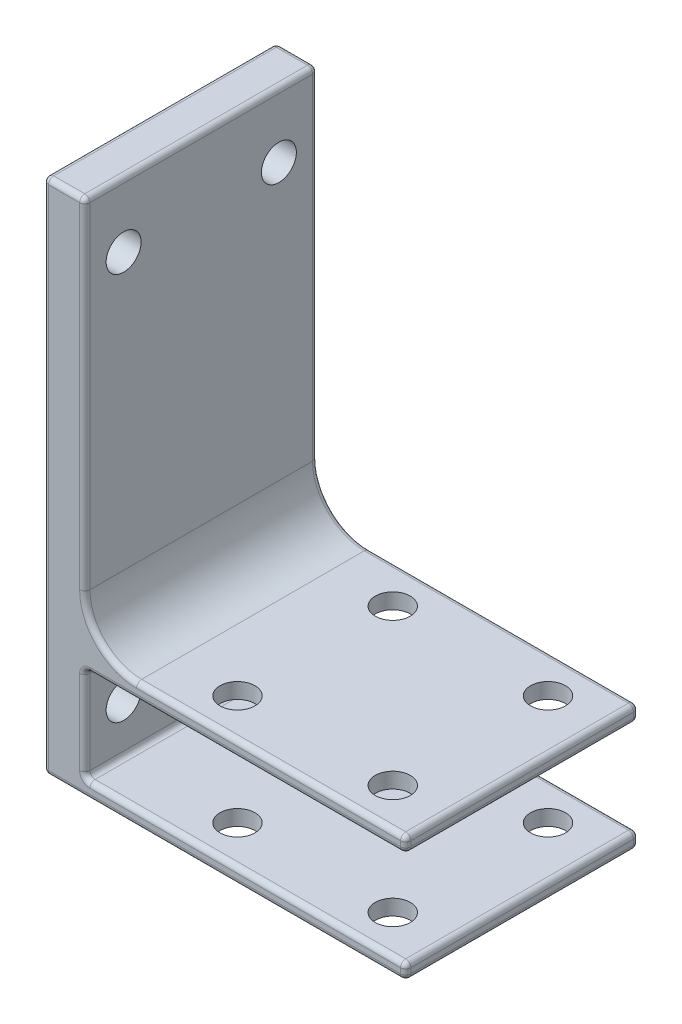
SolidWorks part; units mm, degrees
material "Nylon 6/10"
ref_plane "Front Plane" through (0, 0, 0) normal (0, 0, 1) x (1, 0, 0)
ref_plane "Top Plane" through (0, 0, 0) normal (0, 1, 0) x (1, 0, 0)
ref_plane "Right Plane" through (0, 0, 0) normal (1, 0, 0) x (0, 0, -1)
sketch "Sketch1" plane through (0, 0, 0) normal (0, 0, 1) x (1, 0, 0)
  line L0 (0, 0) -> (0, 100)
  line L1 (0, 100) -> (8, 100)
  line L2 (8, 100) -> (8, 3)
  line L3 (8, 3) -> (70, 3)
  line L4 (70, 3) -> (70, 0)
  line L5 (70, 0) -> (0, 0)
  dimension "D2" = 70
  dimension "D3" = 8
  dimension "D4" = 100
extrude "base" add sketch "Sketch1" along normal blind 45
sketch "Sketch2" plane through (8, 0, 0) normal (1, 0, 0) x (0, 0, -1)
  line L0 (-45, 3) -> (-45, 100) construction
  line L1 (-45, 24.25) -> (0, 24.25)
  line L2 (-45, 24.25) -> (-45, 21.25)
  line L3 (-45, 21.25) -> (0, 21.25)
  line L4 (0, 24.25) -> (0, 21.25)
  line L5 (0, 3) -> (0, 100) construction
  line L6 (-45, 3) -> (0, 3) construction
  dimension "D2" = 18.25
extrude "top skin" add sketch "Sketch2" along normal up to surface (62 mm away) up to face at (70, 1.5, 22.5)
hole_wizard "slider bolt hole pattern" positions "Sketch3" profile "Sketch4" hole size "1/4" standard "ANSI Inch" end condition through all
sketch "Sketch3" plane through (8, 0, 0) normal (1, 0, 0) x (0, 0, -1)
  line L1 (-37.5, 87.5) -> (-7.5, 87.5)
  line L2 (-37.5, 87.5) -> (-37.5, 12.5)
  line L3 (-37.5, 12.5) -> (-7.5, 12.5)
  line L4 (-7.5, 87.5) -> (-7.5, 12.5)
  line L5 (-22.5, 12.5) -> (-22.5, 0) construction
  line L6 (-45, 0) -> (0, 0) construction
  line L8 (-22.5, 87.5) -> (-22.5, 100) construction
  line L9 (-45, 100) -> (0, 100) construction
  point P0 (-37.5, 87.5)
  point P1 (-7.5, 12.5)
  point P60 (-37.5, 12.5)
  point P61 (-7.5, 87.5)
  dimension "D1" = 75
  dimension "D2" = 30
sketch "Sketch4" plane through (8, 87.5, 37.5) normal (0, 1, 0) x (0, 0, -1)
  line L0 (0, 0) -> (0, 8)
  line L1 (0, 8) -> (3.3782, 8)
  line L2 (3.3782, 8) -> (3.3782, 0)
  line L5 (3.3782, 0) -> (0, 0)
  line L11 (0, -6.35) -> (0, 107.95) construction
  dimension "Thru Hole Dia." = 6.7564
  dimension "Thru Hole Depth" = 8
hole_wizard "desktop bolt hole pattern" positions "Sketch5" profile "Sketch6" hole size "1/4" standard "ANSI Inch" end condition through all
sketch "Sketch5" plane through (0, 24.25, 0) normal (0, 1, 0) x (1, 0, 0)
  line L1 (30, -7.5) -> (60, -7.5)
  line L2 (30, -7.5) -> (30, -37.5)
  line L3 (30, -37.5) -> (60, -37.5)
  line L4 (60, -7.5) -> (60, -37.5)
  line L5 (60, -22.5) -> (70, -22.5)
  line L6 (70, -45) -> (70, 0) construction
  point P1 (30, -7.5)
  point P2 (60, -37.5)
  point P97 (30, -37.5)
  point P98 (60, -7.5)
  dimension "D2" = 30
  dimension "D1" = 10
  dimension "D3" = 30
sketch "Sketch6" plane through (30, 24.25, 7.5) normal (1, 0, 0) x (0, 0, 1)
  line L0 (0, 0) -> (0, 24.25)
  line L1 (0, 24.25) -> (3.3782, 24.25)
  line L2 (3.3782, 24.25) -> (3.3782, 0)
  line L5 (3.3782, 0) -> (0, 0)
  line L11 (0, -6.35) -> (0, 107.95) construction
  dimension "Thru Hole Dia." = 6.7564
  dimension "Thru Hole Depth" = 24.25
fillet "visible corner fillet" radius 10 1 edges at (8, 24.25, 22.5)
fillet "Fillet2" radius 1 31 edges at (70, 0, 22.5) (70, 3, 22.5) (70, 24.25, 22.5) (70, 21.25, 22.5) (70, 1.5, 0) (39, 3, 0) (8, 12.125, 0) (39, 21.25, 0) (70, 22.75, 0) (44, 24.25, 0) (10.9289, 27.1789, 0) (8, 67.125, 0) (4, 100, 0) (35, 0, 0) (0, 100, 22.5) (0, 0, 22.5) (0, 50, 0) (0, 50, 45) (4, 100, 45) (8, 67.125, 45) (10.9289, 27.1789, 45) (44, 24.25, 45) (70, 22.75, 45) (39, 21.25, 45) (8, 12.125, 45) (39, 3, 45) (70, 1.5, 45) (35, 0, 45) (8, 3, 22.5) (8, 21.25, 22.5) (8, 100, 22.5)
equation "\"board_thickness\" = 18mm"
equation "\"way_width\"= 75mm"
equation "\"way_thickness\"= 50mm"
equation "\"radial_clearance\"= 0.1mm"
equation "\"slider_width\"= \"way_width\"-2* \"radial_clearance\""
equation "\"slider_thickness\" = \"way_thickness\" - 2 * \"radial_clearance\""
equation "\"column_width\"= \"way_width\" + 2 * \"board_thickness\""
equation "\"boxway_slot_width\" = 50mm"
equation "\"keeper_rail_width\" = (\"column_width\" - \"boxway_slot_width\")/2"
equation "\"slider_length\" = 125mm"
equation "\"nut_diameter\"= 22mm"
equation "\"nut_length\"= 15mm"
equation "\"leadscrew_diameter\"= 10mm"
equation "\"leadscrew_radial_clearance\"= 1mm"
equation "\"bearing_bolt_pattern_width\" = 30mm"
equation "\"bearing_bolt_pattern_height\" = 75mm"
equation "\"desktop_bolt_pattern_width\" = 30mm"
equation "\"desktop_bolt_pattern_height\" = 30mm"
equation "\"bearing_bolt_nut_counterbore_diameter\" = 12mm"
equation "\"bearing_bolt_nut_counterbore_depth\"= 10mm"
equation "\"desktop_depth\"= 500mm"
equation "\"desktop_width\"= 650mm"
equation "\"desktop_thickness\"= 18mm"
equation "\"leg_height\"=100mm"
equation "\"leg_width\"=18mm"
equation "\"leg_length\"=500mm"
equation "\"lap_joint_height\" = 50mm"
equation "\"lap_dowel_diameter\"= 8mm"
equation "\"lap_dowel_hole_z_spacing\"=30"
equation "\"skin_thicknes\"=3"
equation "\"D1@Sketch1\"=\"skin_thicknes\""
equation "\"D1@Sketch2\"=\"skin_thicknes\""
equation "\"D2@Sketch2\"=\"desktop_thickness\" + 0.25"
equation "\"D1@Sketch3\"=\"bearing_bolt_pattern_height\""
equation "\"D2@Sketch3\"=\"bearing_bolt_pattern_width\""
equation "\"D2@Sketch5\"=\"desktop_bolt_pattern_width\""
equation "\"D3@Sketch5\"=\"desktop_bolt_pattern_height\""
